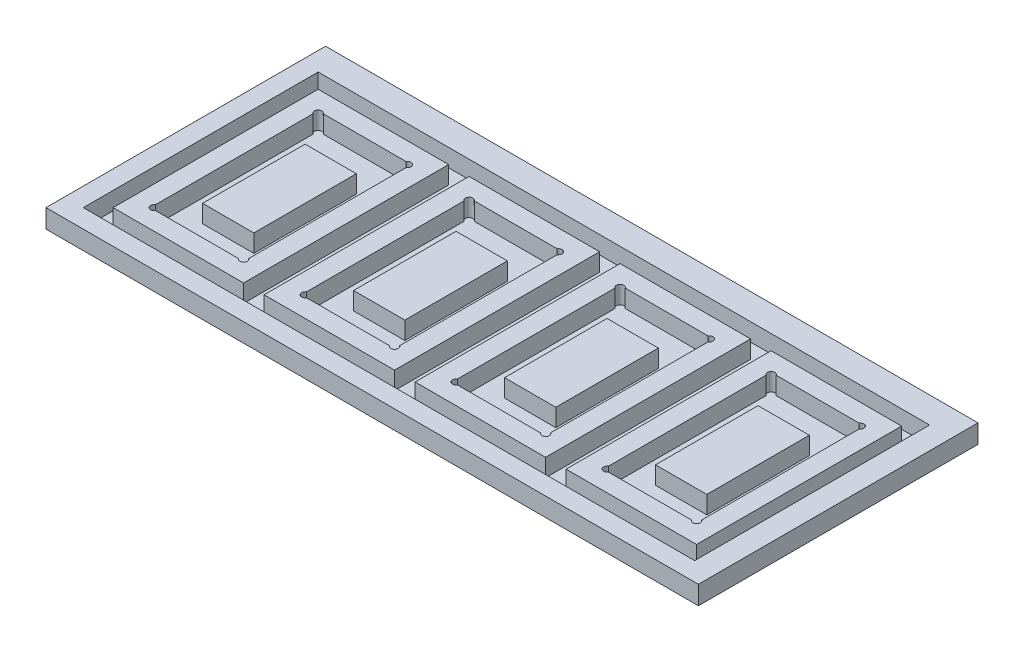
SolidWorks part; units mm, degrees
material "6061 Alloy"
ref_plane "Front Plane" through (0, 0, 0) normal (0, 0, 1) x (1, 0, 0)
ref_plane "Top Plane" through (0, 0, 0) normal (0, 1, 0) x (1, 0, 0)
ref_plane "Right Plane" through (0, 0, 0) normal (1, 0, 0) x (0, 0, -1)
sketch "Sketch1" plane through (0, 0, 0) normal (0, 1, 0) x (1, 0, 0)
  line L1 (-175, -75) -> (175, -75)
  line L2 (-175, -75) -> (-175, 75)
  line L3 (-175, 75) -> (175, 75)
  line L4 (175, -75) -> (175, 75)
  line L5 (-175, -75) -> (175, 75) construction
  line L6 (-175, 75) -> (175, -75) construction
  point P0 (0, 0)
  dimension "D1" = 350
  dimension "D2" = 150
extrude "Boss-Extrude1" add sketch "Sketch1" along normal blind 10
sketch "Sketch2" plane through (0, 10, 0) normal (0, 1, 0) x (1, 0, 0)
  line L0 (98.7562, 43) -> (143.2438, 43)
  line L1 (86, -57) -> (156, -57)
  line L2 (86, -57) -> (86, 53)
  line L3 (86, 53) -> (156, 53)
  line L4 (156, -57) -> (156, 53)
  line L5 (86, -57) -> (156, 53) construction
  line L6 (86, 53) -> (156, -57) construction
  line L7 (146, -44.2438) -> (146, 40.2438)
  line L8 (98.7562, -47) -> (143.2438, -47)
  line L9 (96, -44.2438) -> (96, 40.2438)
  line L10 (96, 43) -> (146, 43) construction
  line L11 (96, -47) -> (96, 43) construction
  line L12 (146, -47) -> (146, 43) construction
  line L13 (96, -47) -> (146, -47) construction
  line L14 (-175, -75) -> (175, -75) construction
  line L15 (108, 24) -> (135.5, 24)
  line L16 (108, 24) -> (108, -31)
  line L17 (108, -31) -> (135.5, -31)
  line L18 (135.5, 24) -> (135.5, -31)
  line L24 (96, -47) -> (96, -44.2438) construction
  line L25 (96, -47) -> (98.7562, -47) construction
  line L26 (143.2438, -47) -> (146, -47) construction
  line L27 (146, -47) -> (146, -44.2438) construction
  line L28 (96, 43) -> (97.0607, 41.9393) construction
  line L29 (146, 43) -> (146, 40.2438) construction
  line L30 (96, 43) -> (98.7562, 43) construction
  line L31 (96, 43) -> (96, 40.2438) construction
  line L32 (146, 43) -> (144.9393, 41.9393) construction
  line L33 (146, -47) -> (144.9393, -45.9393) construction
  line L34 (96, -47) -> (97.0607, -45.9393) construction
  line L35 (5, 53) -> (75, 53)
  line L36 (17.7562, 43) -> (62.2438, 43)
  line L37 (75, -57) -> (75, 53)
  line L38 (65, -44.2438) -> (65, 40.2438)
  line L39 (15, -44.2438) -> (15, 40.2438)
  line L40 (5, -57) -> (5, 53)
  line L41 (5, -57) -> (75, -57)
  line L42 (17.7562, -47) -> (62.2438, -47)
  line L43 (27, 24) -> (27, -31)
  line L44 (27, -31) -> (54.5, -31)
  line L45 (54.5, 24) -> (54.5, -31)
  line L46 (27, 24) -> (54.5, 24)
  line L47 (-76, 53) -> (-6, 53)
  line L48 (-63.2438, 43) -> (-18.7562, 43)
  line L49 (-6, -57) -> (-6, 53)
  line L50 (-16, -44.2438) -> (-16, 40.2438)
  line L51 (-66, -44.2438) -> (-66, 40.2438)
  line L52 (-76, -57) -> (-76, 53)
  line L53 (-76, -57) -> (-6, -57)
  line L54 (-63.2438, -47) -> (-18.7562, -47)
  line L55 (-54, 24) -> (-54, -31)
  line L56 (-54, -31) -> (-26.5, -31)
  line L57 (-26.5, 24) -> (-26.5, -31)
  line L58 (-54, 24) -> (-26.5, 24)
  line L59 (-157, 53) -> (-87, 53)
  line L60 (-144.2438, 43) -> (-99.7562, 43)
  line L61 (-87, -57) -> (-87, 53)
  line L62 (-97, -44.2438) -> (-97, 40.2438)
  line L63 (-147, -44.2438) -> (-147, 40.2438)
  line L64 (-157, -57) -> (-157, 53)
  line L65 (-157, -57) -> (-87, -57)
  line L66 (-144.2438, -47) -> (-99.7562, -47)
  line L67 (-135, 24) -> (-135, -31)
  line L68 (-135, -31) -> (-107.5, -31)
  line L69 (-107.5, 24) -> (-107.5, -31)
  line L70 (-135, 24) -> (-107.5, 24)
  line L73 (-175, 75) -> (-175, -75) construction
  line L79 (-165, 61) -> (163, 61)
  line L80 (-165, 61) -> (-165, -65)
  line L81 (-165, -65) -> (163, -65)
  line L82 (163, 61) -> (163, -65)
  arc A4 (146, 40.2438) -> (143.2438, 43) centre (144.9393, 41.9393) ccw
  arc A5 (98.7562, 43) -> (96, 40.2438) centre (97.0607, 41.9393) ccw
  arc A6 (96, -44.2438) -> (98.7562, -47) centre (97.0607, -45.9393) ccw
  arc A7 (143.2438, -47) -> (146, -44.2438) centre (144.9393, -45.9393) ccw
  arc A8 (65, 40.2438) -> (62.2438, 43) centre (63.9393, 41.9393) ccw
  arc A9 (17.7562, 43) -> (15, 40.2438) centre (16.0607, 41.9393) ccw
  arc A10 (62.2438, -47) -> (65, -44.2438) centre (63.9393, -45.9393) ccw
  arc A11 (15, -44.2438) -> (17.7562, -47) centre (16.0607, -45.9393) ccw
  arc A12 (-16, 40.2438) -> (-18.7562, 43) centre (-17.0607, 41.9393) ccw
  arc A13 (-63.2438, 43) -> (-66, 40.2438) centre (-64.9393, 41.9393) ccw
  arc A14 (-18.7562, -47) -> (-16, -44.2438) centre (-17.0607, -45.9393) ccw
  arc A15 (-66, -44.2438) -> (-63.2438, -47) centre (-64.9393, -45.9393) ccw
  arc A16 (-97, 40.2438) -> (-99.7562, 43) centre (-98.0607, 41.9393) ccw
  arc A17 (-144.2438, 43) -> (-147, 40.2438) centre (-145.9393, 41.9393) ccw
  arc A18 (-99.7562, -47) -> (-97, -44.2438) centre (-98.0607, -45.9393) ccw
  arc A19 (-147, -44.2438) -> (-144.2438, -47) centre (-145.9393, -45.9393) ccw
  dimension "D3" = 4
  dimension "D13" = 45
  dimension "D17" = 4
  dimension "D22" = 4
  dimension "D23" = 4
  dimension "D1" = 110
  dimension "D4" = 55
  dimension "D5" = 27.5
  dimension "D6" = 8
  dimension "D7" = 12
  dimension "D8" = 7
  dimension "D9" = 19
  dimension "D10" = 70
  dimension "D11" = 16
  dimension "D12" = 10.5
  dimension "D14" = 1.5
  dimension "D15" = 45
  dimension "D16" = 1.5
  dimension "D18" = 1.5
  dimension "D19" = 45
  dimension "D20" = 1.5
  dimension "D21" = 45
  dimension "D25" = 11
  dimension "D26" = 10
  dimension "D27" = 8
  dimension "D28" = 8
  dimension "D29" = 10
  dimension "D2" = 10
  dimension "D24" = 4
extrude "Cut-Extrude1" cut sketch "Sketch2" against normal blind 9.5 contours L82 L79 L80 L81 L65 L64 L59 L61 L53 L52 L47 L49 L41 L40 L35 L37 L4 L1 L2 L3 | L63 A19 L66 A18 L62 A16 L60 A17 L67 L70 L69 L68 | L51 A15 L54 A14 L50 A12 L48 A13 L55 L58 L57 L56 | L39 A11 L42 A10 L38 A8 L36 A9 L43 L46 L45 L44 | L8 A7 L7 A4 L0 A5 L9 A6 L15 L18 L17 L16 region at (121, 10, -41.9449) region at (40, 10, -41.9449) region at (-41, 10, -41.9449) region at (-122, 10, -41.9449) region at (-2.4628, 10, 2)
sketch "Sketch3" plane through (0, 10, 0) normal (0, 1, 0) x (1, 0, 0)
  line L0 (175, 75) -> (-175, 75) construction
  line L1 (-133, 75) -> (-110, 75)
  line L2 (-133, 75) -> (-133, -75)
  line L3 (-133, -75) -> (-110, -75)
  line L4 (-110, 75) -> (-110, -75)
  line L5 (-175, -75) -> (175, -75) construction
  line L6 (-122, 43) -> (-122, -47) construction
  line L7 (-144.2438, 43) -> (-99.7562, 43) construction
  line L8 (-144.2438, -47) -> (-99.7562, -47) construction
  line L9 (-144.2438, -47) -> (-99.7562, -47) construction
  dimension "D1" = 12
  dimension "D2" = 11
sketch "Sketch4" plane through (0, 10, 0) normal (0, 1, 0) x (1, 0, 0)
  line L0 (-147, -2) -> (-97, -2) construction
  line L1 (-175, 18) -> (-87, 18)
  line L2 (-175, 18) -> (-175, -22)
  line L3 (-175, -22) -> (-87, -22)
  line L4 (-87, 18) -> (-87, -22)
  line L5 (-147, -44.2438) -> (-147, 40.2438) construction
  line L6 (-97, -44.2438) -> (-97, 40.2438) construction
  line L7 (-175, 75) -> (-175, -75) construction
  line L8 (-87, -57) -> (-87, 53) construction
  dimension "D1" = 20
  dimension "D2" = 20
sketch3d "3DSketch1"
  point P0 (-175, 10, 75)
